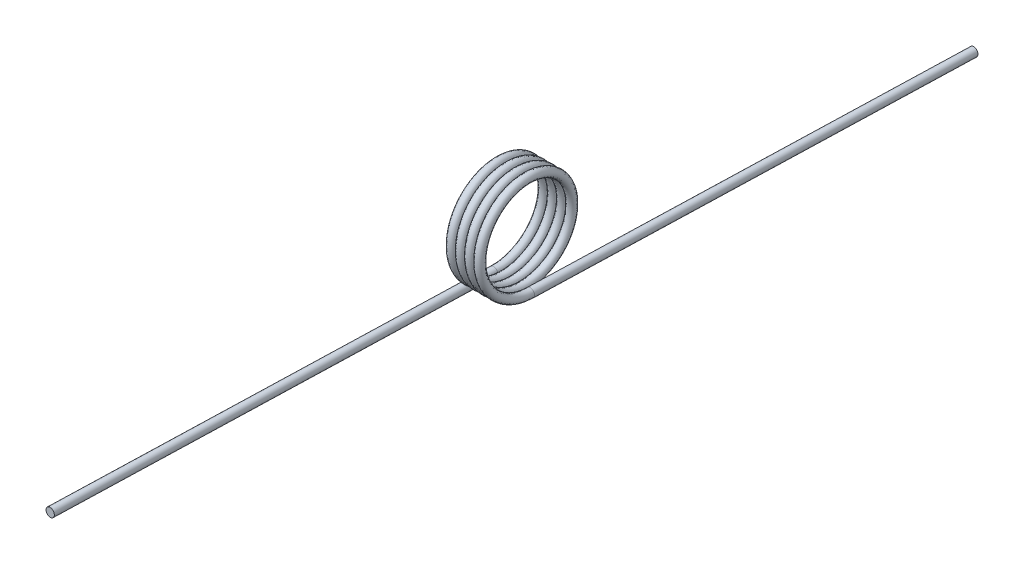
SolidWorks part; units mm, degrees
ref_plane "Front" through (0, 0, 0) normal (0, 0, 1) x (1, 0, 0)
ref_plane "Top" through (0, 0, 0) normal (0, 1, 0) x (1, 0, 0)
ref_plane "Right" through (0, 0, 0) normal (1, 0, 0) x (0, 0, -1)
sketch "Sketch1" plane through (0, 0, 0) normal (1, 0, 0) x (0, 0, -1)
  line L0 (0, 0) -> (0, -1.9431) construction
  line L1 (0, -1.9431) -> (0, -2.1336) construction
  line L2 (0, -2.1336) -> (0, -2.3241) construction
  circle A0 centre (0, 0) radius 1.9431 construction
  circle A1 centre (0, 0) radius 2.3241 construction
  circle A2 centre (0, 0) radius 2.1336
  circle A3 centre (0, -2.1336) radius 0.1905 construction
  circle A4 centre (0, 0) radius 1.3843 construction
  dimension "Wire Dia" = 0.381
  dimension "Spring OD" = 4.6482
  dimension "Max Rod OD" = 2.7686
curve "Helix/Spiral1" pitch 0.4064 height 1.6256 turns 4
ref_plane "Plane1" through (0, -2.1336, 0) normal (0.0303, 0, -0.9995) x (-0.9995, 0, -0.0303)
sketch "Sketch2" plane through (0, -2.1336, 0) normal (0.0303, 0, -0.9995) x (-0.9995, 0, -0.0303)
  circle A0 centre (0, 0) radius 0.1905
  dimension "D1" = 0.381
sweep "Sweep1" add profiles "Sketch2" path "Helix/Spiral1"
sketch "Sketch3" plane through (0, 0, 0) normal (-0.0303, 0, 0.9995) x (0.9995, 0, 0.0303)
  circle A1 centre (0, -2.1336) radius 0.1905
  circle A2 centre (0, -2.1336) radius 0.1905
  dimension "D1" = 0
extrude "Extrude1" add sketch "Sketch3" along normal blind 19.05
sketch "Sketch4" plane through (0.0015, 0, -0.0492) normal (0.0303, 0, -0.9995) x (-0.9959, -0.0856, -0.0302)
  circle A1 centre (-1.4362, -2.2649) radius 0.1905
  circle A2 centre (-1.4362, -2.2649) radius 0.1905
  dimension "D1" = 0
extrude "Extrude2" add sketch "Sketch4" along normal blind 19.05
sketch "Sketch5" plane through (0, 0, 0) normal (1, 0, 0) x (0, 0, -1)
  circle A0 centre (0, 0) radius 1.3843 construction
  circle A1 centre (0, 0) radius 1.3843
equation "\"D4@Helix/Spiral1\"=\"Wire Dia@Sketch1\"+.001"
equation "\"D1@Sketch2\"=\"Wire Dia@Sketch1\""
equation "\"D1@Extrude2\"=\"Leg Length@Extrude1\""
